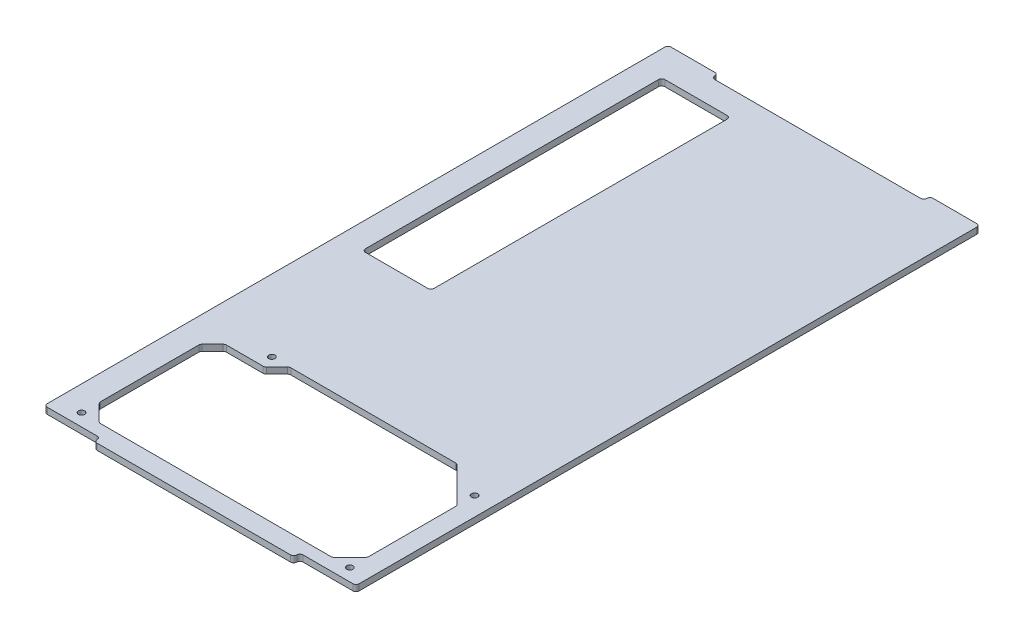
SolidWorks part; units mm, degrees
ref_plane "Front Plane" through (0, 0, 0) normal (0, 0, 1) x (1, 0, 0)
ref_plane "Top Plane" through (0, 0, 0) normal (0, 1, 0) x (1, 0, 0)
ref_plane "Right Plane" through (0, 0, 0) normal (1, 0, 0) x (0, 0, -1)
sketch "Sketch1" plane through (0, 0, 0) normal (0, 1, 0) x (1, 0, 0)
  line L0 (130.175, 0) -> (158.75, 0)
  line L1 (0, 0) -> (28.575, 0)
  line L2 (0, 0) -> (0, 317.5)
  line L3 (0, 317.5) -> (158.75, 317.5)
  line L4 (158.75, 0) -> (158.75, 317.5)
  line L6 (28.575, 0) -> (28.575, -3.175)
  line L7 (28.575, -3.175) -> (130.175, -3.175)
  line L8 (130.175, 0) -> (130.175, -3.175)
  point P9 (79.375, -3.175)
  point P10 (79.375, 317.5)
  dimension "D1" = 158.75
  dimension "D2" = 317.5
  dimension "D3" = 3.175
  dimension "D4" = 101.6
extrude "Boss-Extrude1" add sketch "Sketch1" along normal blind 3.175
sketch "Sketch2" plane through (0, 3.175, 0) normal (0, 1, 0) x (1, 0, 0)
  line L0 (158.75, 317.5) -> (0, 317.5) construction
  line L1 (25.4, 317.5) -> (133.35, 317.5)
  line L2 (25.4, 317.5) -> (25.4, 314.325)
  line L3 (25.4, 314.325) -> (133.35, 314.325)
  line L4 (133.35, 317.5) -> (133.35, 314.325)
  point P6 (79.375, 317.5)
  point P7 (79.375, 317.5)
  dimension "D1" = 107.95
  dimension "D2" = 3.175
extrude "Cut-Extrude1" cut sketch "Sketch2" against normal through all
sketch "Sketch3" plane through (0, 3.175, 0) normal (0, 1, 0) x (1, 0, 0)
  line L0 (21.6803, 6.35) -> (12.7, 15.3303)
  line L1 (45.4928, 79.375) -> (130.7197, 79.375)
  line L2 (12.7, 66.675) -> (12.7, 15.3303)
  line L3 (21.6803, 6.35) -> (140.2447, 6.35)
  line L4 (149.225, 60.8697) -> (149.225, 15.3303)
  line L5 (140.2447, 6.35) -> (149.225, 15.3303)
  line L7 (149.225, 60.8697) -> (130.7197, 79.375)
  line L8 (12.7, 66.675) -> (19.05, 73.025)
  line L9 (6.35, 0) -> (155.575, 0) construction
  line L10 (6.35, 0) -> (6.35, 85.725) construction
  line L11 (6.35, 85.725) -> (155.575, 85.725) construction
  line L12 (155.575, 0) -> (155.575, 85.725) construction
  line L13 (19.05, 73.025) -> (39.1428, 73.025)
  line L14 (39.1428, 73.025) -> (45.4928, 79.375)
  line L15 (130.175, 0) -> (158.75, 0) construction
  line L16 (0, 317.5) -> (0, 0) construction
  circle A0 centre (12.7, 6.35) radius 1.5875
  circle A1 centre (149.225, 6.35) radius 1.5875
  circle A2 centre (149.225, 69.85) radius 1.5875
  circle A3 centre (36.5125, 79.375) radius 1.5875
  dimension "D3" = 3.175
  dimension "D1" = 149.225
  dimension "D2" = 85.725
  dimension "D4" = 6.35
  dimension "D5" = 6.35
  dimension "D6" = 6.35
  dimension "D7" = 15.875
  dimension "D8" = 6.35
  dimension "D9" = 30.1625
  dimension "D10" = 6.35
  dimension "D11" = 12.7
  dimension "D12" = 6.35
  dimension "D13" = 6.35
  dimension "D14" = 135
  dimension "D15" = 6.35
  dimension "D16" = 6.35
  dimension "D18" = 135
extrude "Cut-Extrude2" cut sketch "Sketch3" against normal through all
sketch "Sketch4" plane through (0, 3.175, 0) normal (0, 1, 0) x (1, 0, 0)
  line L0 (0, 317.5) -> (0, 0) construction
  line L1 (12.7, 301.625) -> (47.625, 301.625)
  line L2 (12.7, 301.625) -> (12.7, 149.225)
  line L3 (12.7, 149.225) -> (47.625, 149.225)
  line L4 (47.625, 301.625) -> (47.625, 149.225)
  line L5 (25.4, 314.325) -> (133.35, 314.325) construction
  dimension "D1" = 152.4
  dimension "D2" = 34.925
  dimension "D3" = 12.7
  dimension "D4" = 12.7
extrude "Cut-Extrude3" cut sketch "Sketch4" against normal through all
fillet "Fillet1" radius 1.5875 26 edges at (25.4, 1.5875, -314.325) (25.4, 1.5875, -317.5) (0, 1.5875, -317.5) (0, 1.5875, 0) (28.575, 1.5875, 0) (28.575, 1.5875, 3.175) (130.175, 1.5875, 3.175) (130.175, 1.5875, 0) (158.75, 1.5875, 0) (158.75, 1.5875, -317.5) (133.35, 1.5875, -317.5) (133.35, 1.5875, -314.325) (140.2447, 1.5875, -6.35) (149.225, 1.5875, -15.3303) (149.225, 1.5875, -60.8697) (130.7197, 1.5875, -79.375) (45.4928, 1.5875, -79.375) (39.1428, 1.5875, -73.025) (19.05, 1.5875, -73.025) (12.7, 1.5875, -66.675) (21.6803, 1.5875, -6.35) (12.7, 1.5875, -15.3303) (12.7, 1.5875, -149.225) (47.625, 1.5875, -149.225) (12.7, 1.5875, -301.625) (47.625, 1.5875, -301.625)
